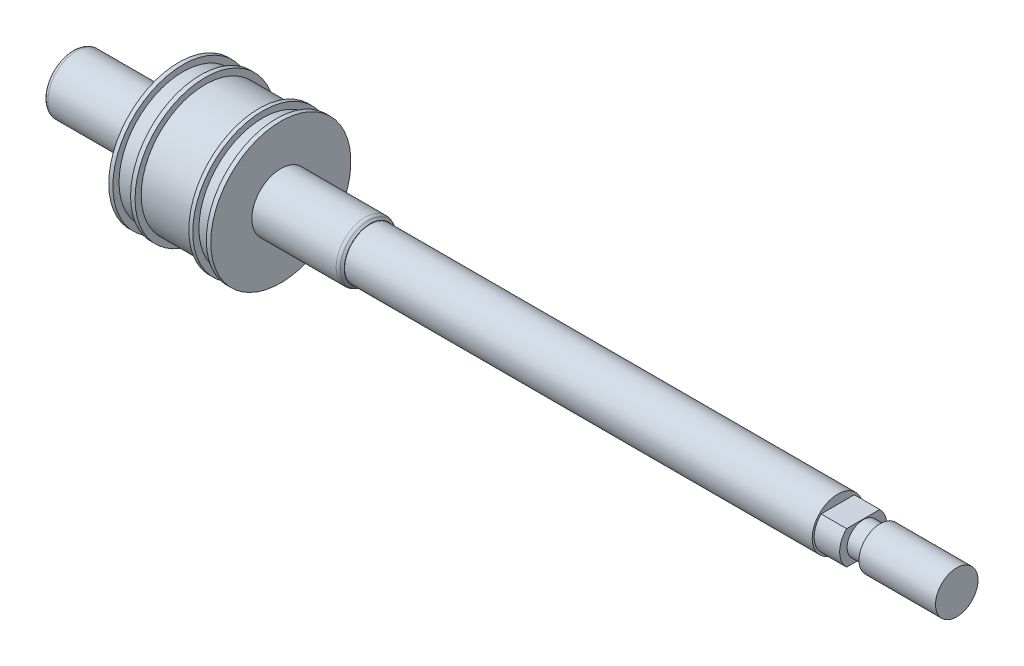
SolidWorks part; units mm, degrees
ref_plane "Front Plane" through (0, 0, 0) normal (0, 0, 1) x (1, 0, 0)
ref_plane "Top Plane" through (0, 0, 0) normal (0, 1, 0) x (1, 0, 0)
ref_plane "Right Plane" through (0, 0, 0) normal (1, 0, 0) x (0, 0, -1)
sketch "Sketch1" plane through (0, 0, 0) normal (1, 0, 0) x (0, 0, -1)
  circle A0 centre (0, 0) radius 6
  dimension "D1" = 12
extrude "Extrude1" add sketch "Sketch1" along normal blind 180
sketch "Sketch2" plane through (180, 0, 0) normal (1, 0, 0) x (0, 0, -1)
  line L0 (-3.9062, 3.924) -> (3.9062, 3.924)
  line L1 (3.9062, -3.924) -> (-3.9062, -3.924)
  arc A0 (-3.9062, 3.924) -> (-3.9062, -3.924) centre (0, 0) ccw
  arc A1 (3.9062, -3.924) -> (3.9062, 3.924) centre (0, 0) ccw
extrude "Extrude2" add sketch "Sketch2" along normal blind 6
sketch "Sketch3" plane through (186, 0, 0) normal (1, 0, 0) x (0, 0, -1)
  circle A0 centre (0, 0) radius 3.7883
extrude "Extrude3" add sketch "Sketch3" along normal blind 4
sketch "Sketch4" plane through (190, 0, 0) normal (1, 0, 0) x (0, 0, -1)
  circle A0 centre (0, 0) radius 5
  dimension "D1" = 10
extrude "Extrude4" add sketch "Sketch4" along normal blind 18
sketch "Sketch6" plane through (208, 0, 0) normal (1, 0, 0) x (0, 0, -1)
  circle A0 centre (0, 0) radius 5
curve "Helix/Spiral1" pitch 1.25 height 18 turns 14.4
sketch "Sketch7" plane through (180, 0, 0) normal (1, 0, 0) x (0, 0, -1)
  circle A0 centre (0, 0) radius 6.9765
sketch "Sketch8" plane through (0, 0, 0) normal (-1, 0, 0) x (0, 0, 1)
  circle A0 centre (0, 0) radius 6.8255
extrude "Extrude5" add sketch "Sketch8" against normal blind 70
chamfer "Chamfer1" distance 0.75 angle 45 1 edges at (70, 0, 6.8255)
fillet "Fillet1" radius 1 1 edges at (69.25, 0, 6.8255)
fillet "Fillet2" radius 1 1 edges at (0, 0, 6.8255)
ref_plane "Plane1" through (25, 0, 0) normal (-1, 0, 0) x (0, 0, 1)
sketch "Sketch9" plane through (25, 0, 0) normal (-1, 0, 0) x (0, 0, 1)
  circle A0 centre (0, 0) radius 16.4794
extrude "Extrude6" add sketch "Sketch9" against normal blind 24
sketch "Sketch10" plane through (0, 0, 0) normal (0, 1, 0) x (1, 0, 0)
  line L1 (25.973, 16.8481) -> (30.1297, 16.8481)
  line L2 (25.973, 16.8481) -> (25.973, 15.0351)
  line L3 (25.973, 15.0351) -> (30.1297, 15.0351)
  line L4 (30.1297, 16.8481) -> (30.1297, 15.0351)
  line L5 (31.1911, 16.8481) -> (43.8383, 16.8481)
  line L6 (31.1911, 16.8481) -> (31.1911, 15.0351)
  line L7 (31.1911, 15.0351) -> (43.8383, 15.0351)
  line L8 (43.8383, 16.8481) -> (43.8383, 15.0351)
  line L9 (44.7669, 16.8481) -> (47.9508, 16.8481)
  line L10 (44.7669, 16.8481) -> (44.7669, 15.0351)
  line L11 (44.7669, 15.0351) -> (47.9508, 15.0351)
  line L12 (47.9508, 16.8481) -> (47.9508, 15.0351)
sketch "Sketch11" plane through (0, 0, 0) normal (0, 1, 0) x (1, 0, 0)
  line L0 (0, 0) -> (208, 0)
  line L1 (208, -5) -> (208, 5) construction
ref_axis "Axis1" through (208, 0, 0) along (-1, 0, 0)
revolve "Cut-Revolve1" cut sketch "Sketch10" angle 360 about L0
